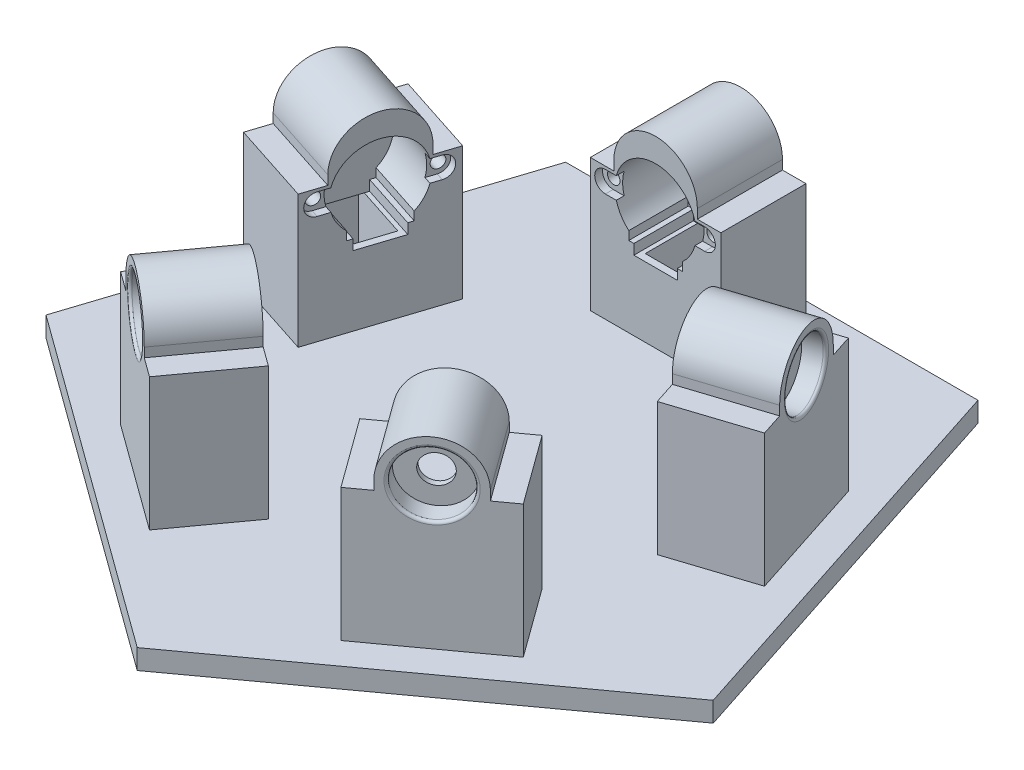
SolidWorks part; units mm, degrees
ref_plane "Front Plane" through (0, 0, 0) normal (0, 0, 1) x (1, 0, 0)
ref_plane "Top Plane" through (0, 0, 0) normal (0, 1, 0) x (1, 0, 0)
ref_plane "Right Plane" through (0, 0, 0) normal (1, 0, 0) x (0, 0, -1)
ref_plane "Psuedo R-offset" through (0, 0, -80) normal (0, 0, 1) x (1, 0, 0)
sketch "Sketch12" plane through (0, 0, 0) normal (0, 1, 0) x (1, 0, 0)
  line L1 (0, -123.6068) -> (117.5571, -38.1966)
  line L2 (117.5571, -38.1966) -> (72.6543, 100)
  line L3 (72.6543, 100) -> (-72.6543, 100)
  line L4 (-72.6543, 100) -> (-117.5571, -38.1966)
  line L5 (-117.5571, -38.1966) -> (0, -123.6068)
  line L6 (-55, 80) -> (55, 80) construction
  circle A0 centre (0, 0) radius 100 construction
  dimension "D1" = 20
extrude "Base" add sketch "Sketch12" against normal blind 7
ref_axis "Axis1" through (0, -9.448, 0) along (0, 1, 0)
sketch "Sketch2" plane through (0, 0, -80) normal (0, 0, 1) x (1, 0, 0)
  line L0 (-7.65, 28.18) -> (-7.65, 24.59)
  line L1 (-7.65, 24.59) -> (7.65, 24.59)
  line L2 (7.65, 24.59) -> (7.65, 28.18)
  line L3 (7.65, 28.18) -> (9.45, 28.18)
  line L4 (9.45, 28.18) -> (9.45, 31.2)
  line L5 (-7.65, 28.18) -> (-9.45, 28.18)
  line L6 (-9.45, 28.18) -> (-9.45, 31.2)
  line L7 (-14.7095, 50) -> (-23, 50)
  line L8 (-23, 50) -> (-23, 0)
  line L10 (14.7095, 50) -> (23, 50)
  line L11 (23, 50) -> (23, 0)
  line L13 (-23, 0) -> (23, 0)
  line L14 (0, 0) -> (117.5571, 0) construction
  arc A0 (14.7095, 50) -> (-14.7095, 50) centre (0, 50) ccw
  arc A4 (9.45, 31.2) -> (-9.45, 31.2) centre (0, 41.9991) ccw
  dimension "D1" = 8.2905
  dimension "D12" = 3.59
  dimension "D16" = 14.35
  dimension "D17" = 14.7095
  dimension "D2" = 8.2905
  dimension "D3" = 25.41
  dimension "D5" = 50
  dimension "D7" = 46
  dimension "D9" = 3.02
  dimension "D10" = 1.8
  dimension "D11" = 1.8
  dimension "D13" = 15.3
  dimension "D14" = 3.02
  dimension "D15" = 3.59
extrude "Boss-Extrude1" add sketch "Sketch2" along normal blind 20.95
sketch "Sketch3" plane through (0, 0, -80) normal (0, 0, 1) x (1, 0, 0)
  line L7 (-14.7095, 50) -> (-23, 50)
  line L8 (-23, 50) -> (-23, 0)
  line L9 (14.7095, 50) -> (23, 50)
  line L10 (23, 50) -> (23, 0)
  line L11 (-23, 0) -> (23, 0)
  line L12 (23, 50) -> (14.7095, 50) construction
  line L13 (-23, 50) -> (-23, 0) construction
  line L17 (-23, 0) -> (23, 0) construction
  line L19 (23, 0) -> (23, 50) construction
  arc A0 (14.7095, 50) -> (-14.7095, 50) centre (0, 50) ccw
  arc A1 (14.7095, 50) -> (-14.7095, 50) centre (0, 50) ccw construction
  dimension "D1" = 0
extrude "Boss-Extrude2" add sketch "Sketch3" against normal blind 9.05
sketch "Sketch6" plane through (0, 0, -59.05) normal (0, 0, 1) x (1, 0, 0)
  line L0 (-14.7095, 50) -> (-23, 50) construction
  line L1 (-23, 50) -> (-23, 0) construction
  line L2 (23, 50) -> (14.7095, 50) construction
  line L3 (23, 0) -> (23, 50) construction
  circle A0 centre (-17.5, 42) radius 2.2
  circle A1 centre (17.5, 42) radius 2.2
  dimension "D1" = 8
  dimension "D2" = 5.5
  dimension "D3" = 4.4
  dimension "D4" = 8
  dimension "D5" = 5.5
  dimension "D6" = 4.4
extrude "Cut-Extrude2" cut sketch "Sketch6" against normal blind 10
sketch "Sketch7" plane through (0, 0, -59.05) normal (0, 0, 1) x (1, 0, 0)
  line L0 (-17.7, 42) -> (17.3, 42) construction
  line L3 (-17.7, 45.75) -> (17.3, 45.75)
  line L4 (-17.7, 38.25) -> (17.3, 38.25)
  arc A2 (-17.7, 45.75) -> (-17.7, 38.25) centre (-17.7, 42) ccw
  arc A3 (17.3, 38.25) -> (17.3, 45.75) centre (17.3, 42) ccw
  circle A4 centre (-17.5, 42) radius 2.2 construction
  circle A5 centre (-17.5, 42) radius 2.2 construction
  circle A6 centre (17.5, 42) radius 2.2 construction
  point P2 (-0.2, 42)
  dimension "D2" = 7.5
  dimension "D3" = 1.75
  dimension "D4" = 1.75
  dimension "D1" = 3.75
extrude "Cut-Extrude3" cut sketch "Sketch7" against normal blind 2.75
sketch "Sketch8" plane through (0, 0, -59.05) normal (0, 0, 1) x (1, 0, 0)
  line L0 (-14.7095, 50) -> (-23, 50) construction
  line L1 (-14.7095, 50) -> (-23, 50)
  line L2 (-14.7095, 50) -> (-14.7095, 46.75)
  line L3 (-14.7095, 46.75) -> (-23, 46.75)
  line L4 (-23, 50) -> (-23, 46.75)
  line L5 (14.7095, 50) -> (23, 50)
  line L6 (14.7095, 50) -> (14.7095, 46.75)
  line L7 (14.7095, 46.75) -> (23, 46.75)
  line L8 (23, 50) -> (23, 46.75)
  line L9 (-23, 50) -> (-23, 0) construction
  line L10 (-13.8511, 45.75) -> (-17.7, 45.75) construction
  line L11 (17.3, 45.75) -> (13.8511, 45.75) construction
  line L12 (23, 0) -> (23, 50) construction
  line L13 (23, 50) -> (14.7095, 50) construction
  dimension "D2" = 1
  dimension "D3" = 1
extrude "Cut-Extrude4" cut sketch "Sketch8" along normal through all both and the other way through all
sketch "Sketch11" plane through (0, 0, -89.05) normal (0, 0, -1) x (-1, 0, 0)
  circle A0 centre (0, 50) radius 11.15
  arc A1 (14.7095, 50) -> (-14.7095, 50) centre (0, 50) ccw construction
  dimension "D1" = 22.3
extrude "Bearing Hole" cut sketch "Sketch11" against normal blind 7
sketch "Sketch9" plane through (0, 24.59, -19.25) normal (0, 1, 0) x (-1, 0, 0)
  line L0 (7.65, -39.8) -> (-7.65, -39.8) construction
  line L1 (-6.15, -42.3) -> (6.15, -42.3)
  line L2 (-6.15, -42.3) -> (-6.15, -63.8)
  line L3 (-6.15, -63.8) -> (6.15, -63.8)
  line L4 (6.15, -42.3) -> (6.15, -63.8)
  line L8 (-7.65, -39.8) -> (-7.65, -60.75) construction
  line L9 (7.65, -39.8) -> (7.65, -60.75) construction
  line L10 (7.65, -69.8) -> (-7.65, -69.8) construction
  dimension "D1" = 2.5
  dimension "D2" = 1.5
  dimension "D3" = 1.5
  dimension "D4" = 6
extrude "Wire Hole" cut sketch "Sketch9" against normal blind 50
sketch "Sketch14" plane through (0, 0, -82.05) normal (0, 0, -1) x (-1, 0, 0)
  circle A0 centre (0, 50) radius 5
  dimension "D1" = 10
extrude "Cut-Extrude5" cut sketch "Sketch14" against normal through all
fillet "Fillet1" radius 1 1 edges at (-11.15, 50, -89.05)
pattern_circular "CirPattern2" count 5 over 360 about axis through (0, -9.448, 0) along (0, 1, 0) of "Wire Hole", "Bearing Hole", "Cut-Extrude4", "Cut-Extrude3", "Cut-Extrude2", "Boss-Extrude2", "Boss-Extrude1"
ref_plane "R_Offset (measure)" through (0, 0, -74.05) normal (0, 0, 1) x (1, 0, 0)
sketch "Sketch13" plane through (0, 0, 0) normal (0, 1, 0) x (1, 0, 0)
  circle A0 centre (0, 0) radius 5
  dimension "D1" = 10
extrude "Camera Hole" cut sketch "Sketch13" against normal through all
